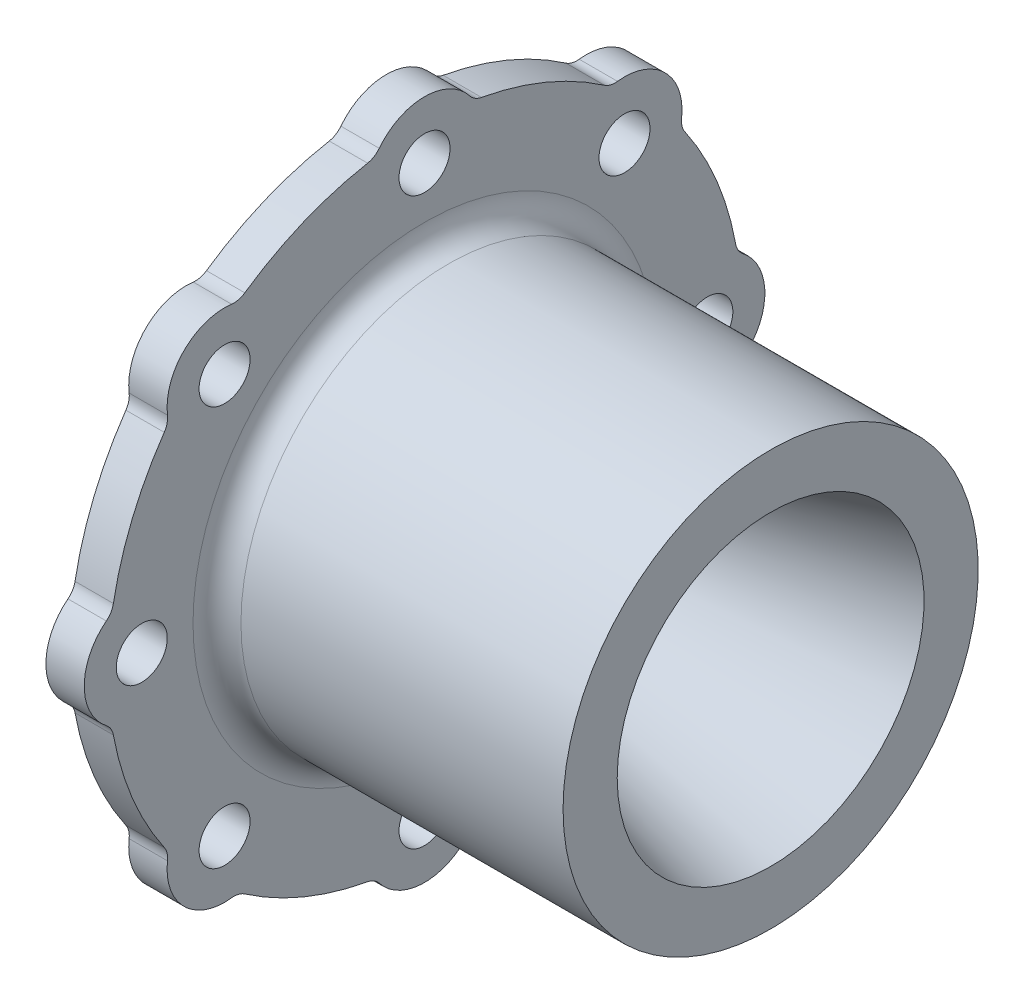
SolidWorks part; units mm, degrees
ref_plane "Front Plane" through (0, 0, 0) normal (0, 0, 1) x (1, 0, 0)
ref_plane "Top Plane" through (0, 0, 0) normal (0, 1, 0) x (1, 0, 0)
ref_plane "Right Plane" through (0, 0, 0) normal (1, 0, 0) x (0, 0, -1)
sketch "Sketch1" plane through (0, 0, 0) normal (0, 0, 1) x (1, 0, 0)
  line L20 (0, 0) -> (32.997, 0) construction
  line L33 (10.9827, 12.3114) -> (21.0157, 12.3114)
  line L34 (10.9827, 12.3114) -> (0, 25.4)
  line L37 (0, 25.4) -> (0, 66.87)
  line L38 (0, 66.87) -> (5.08, 66.87)
  line L39 (5.08, 66.87) -> (5.08, 27.5)
  line L43 (50.9297, 27.5) -> (50.9297, 20.3268)
  line L52 (50.9297, 20.3268) -> (21.0157, 12.3114)
  line L53 (50.9297, 27.5) -> (5.08, 27.5)
  point P1 (2.54, 66.87)
  point P12 (10.9827, 12.3114)
  point P24 (21.0157, 12.3114)
  dimension "D1" = 12.3114
  dimension "D2" = 25.4
  dimension "D5" = 5.08
  dimension "D10" = 15
  dimension "D8" = 20.3268
  dimension "D3" = 27.5
  dimension "D4" = 66.87
  dimension "D6" = 10.033
  dimension "D7" = 50
revolve "Nozzle" add sketch "Sketch1" angle 360 about L20
fillet "Rao outlet radius" radius 4.7029 1 edges at (21.0157, 0, 12.3114)
sketch "Sketch2" plane through (0, 0, 0) normal (-1, 0, 0) x (0, 0, 1)
  point P0 (37.465, 0)
  point P1 (26.4918, -26.4918)
  point P5 (0, -37.465)
  point P6 (-26.4918, -26.4918)
  point P7 (-37.465, 0)
  point P8 (-26.4918, 26.4918)
  point P9 (0, 37.465)
  point P10 (26.4918, 26.4918)
  point P11 (0, 0)
  dimension "D1" = 37.465
hole_wizard "1/4 Clearance Hole1" positions "Sketch2" profile "Sketch3" hole size "1/4" standard "ANSI Inch" end condition through all
sketch "Sketch3" plane through (0, 0, 37.465) normal (0, 1, 0) x (0, 0, 1)
  line L0 (0, 0) -> (0, 50.9297)
  line L1 (0, 50.9297) -> (3.3782, 50.9297)
  line L2 (3.3782, 50.9297) -> (3.3782, 0)
  line L5 (3.3782, 0) -> (0, 0)
  line L11 (0, -6.35) -> (0, 107.95) construction
  dimension "Thru Hole Dia." = 6.7564
  dimension "Thru Hole Depth" = 50.9297
sketch "Sketch5" plane through (0, 0, 0) normal (1, 0, 0) x (0, 0, -1)
  line L0 (0, 0) -> (0, 85.5504) construction
  arc A32 (6.0027, 42.1589) -> (-6.0027, 42.1589) centre (0, 37.465) ccw
  arc A33 (17.8531, 37.9172) -> (7.5462, 41.225) centre (0, 0) ccw
  arc A51 (-7.5462, 41.225) -> (-14.1874, 39.4356) centre (0, 0) ccw
  arc A69 (6.0027, 42.1589) -> (7.5462, 41.225) centre (8.0035, 43.7235) ccw
  arc A70 (-6.0027, 42.1589) -> (-7.5462, 41.225) centre (-8.0035, 43.7235) cw
  arc A72 (34.0554, 25.5663) -> (25.5663, 34.0554) centre (26.4918, 26.4918) ccw
  arc A73 (39.4356, 14.1874) -> (34.4865, 23.8145) centre (0, 0) ccw
  arc A74 (23.8145, 34.4865) -> (17.8531, 37.9172) centre (0, 0) ccw
  arc A75 (34.0554, 25.5663) -> (34.4865, 23.8145) centre (36.5765, 25.2578) ccw
  arc A76 (25.5663, 34.0554) -> (23.8145, 34.4865) centre (25.2578, 36.5765) cw
  arc A77 (42.1589, -6.0027) -> (42.1589, 6.0027) centre (37.465, 0) ccw
  arc A78 (37.9172, -17.8531) -> (41.225, -7.5462) centre (0, 0) ccw
  arc A79 (41.225, 7.5462) -> (39.4356, 14.1874) centre (0, 0) ccw
  arc A80 (42.1589, -6.0027) -> (41.225, -7.5462) centre (43.7235, -8.0035) ccw
  arc A81 (42.1589, 6.0027) -> (41.225, 7.5462) centre (43.7235, 8.0035) cw
  arc A82 (25.5663, -34.0554) -> (34.0554, -25.5663) centre (26.4918, -26.4918) ccw
  arc A83 (14.1874, -39.4356) -> (23.8145, -34.4865) centre (0, 0) ccw
  arc A84 (34.4865, -23.8145) -> (37.9172, -17.8531) centre (0, 0) ccw
  arc A85 (25.5663, -34.0554) -> (23.8145, -34.4865) centre (25.2578, -36.5765) ccw
  arc A86 (34.0554, -25.5663) -> (34.4865, -23.8145) centre (36.5765, -25.2578) cw
  arc A87 (-6.0027, -42.1589) -> (6.0027, -42.1589) centre (0, -37.465) ccw
  arc A88 (-14.2148, -39.4257) -> (-7.5462, -41.225) centre (0, 0) ccw
  arc A89 (7.5462, -41.225) -> (14.1874, -39.4356) centre (0, 0) ccw
  arc A90 (-6.0027, -42.1589) -> (-7.5462, -41.225) centre (-8.0035, -43.7235) ccw
  arc A91 (6.0027, -42.1589) -> (7.5462, -41.225) centre (8.0035, -43.7235) cw
  arc A92 (-34.0554, -25.5663) -> (-25.5663, -34.0554) centre (-26.4918, -26.4918) ccw
  arc A93 (-37.9194, -17.8486) -> (-34.4865, -23.8145) centre (0, 0) ccw
  arc A94 (-23.8145, -34.4865) -> (-14.2148, -39.4257) centre (0, 0) ccw
  arc A95 (-34.0554, -25.5663) -> (-34.4865, -23.8145) centre (-36.5765, -25.2578) ccw
  arc A96 (-25.5663, -34.0554) -> (-23.8145, -34.4865) centre (-25.2578, -36.5765) cw
  arc A97 (-42.1589, 6.0027) -> (-42.1589, -6.0027) centre (-37.465, 0) ccw
  arc A98 (-39.4483, 14.1519) -> (-41.225, 7.5462) centre (0, 0) ccw
  arc A99 (-41.225, -7.5462) -> (-37.9194, -17.8486) centre (0, 0) ccw
  arc A100 (-42.1589, 6.0027) -> (-41.225, 7.5462) centre (-43.7235, 8.0035) ccw
  arc A101 (-42.1589, -6.0027) -> (-41.225, -7.5462) centre (-43.7235, -8.0035) cw
  arc A102 (-25.5663, 34.0554) -> (-34.0554, 25.5663) centre (-26.4918, 26.4918) ccw
  arc A103 (-14.1874, 39.4356) -> (-23.8145, 34.4865) centre (0, 0) ccw
  arc A104 (-34.4865, 23.8145) -> (-39.4483, 14.1519) centre (0, 0) ccw
  arc A105 (-25.5663, 34.0554) -> (-23.8145, 34.4865) centre (-25.2578, 36.5765) ccw
  arc A106 (-34.0554, 25.5663) -> (-34.4865, 23.8145) centre (-36.5765, 25.2578) cw
  point P69 (0, 0)
  point P78 (-6.5261, 41.3988)
  dimension "D3" = 41.91
  dimension "D4" = 2.54
  dimension "D5" = 37.465
  dimension "D6" = 37.465
  dimension "D1" = 8
extrude "Cut-Extrude1" cut sketch "Sketch5" along normal up to surface (5.08 mm away) flip side to cut up to face at (5.08, 0, 40.8432)
fillet "Fillet1" radius 3.175 1 edges at (5.08, 0, 27.5)
fillet "Rao Inlet radius" radius 18.4671 1 edges at (10.9827, 0, 12.3114)
equation "\"radius\"= 1in"
equation "\"Flange\"= 0.55in"
equation "\"Length\"= 2cm"
equation "\"Flange_Thickness\"= 0.2in"
equation "\"offset\"= 0.625cm"
equation "\"D2@Sketch1\"=\"radius\""
equation "\"throat\" = 0.4847in"
equation "\"hole_dia\"= 0.66cm"
equation "\"D1@Sketch1\"=\"throat\""
equation "\"D5@Sketch1\"=\"Flange_Thickness\""
equation "\"Seal_dia\"= 2.5cm"
equation "\"Seal_depth\"= 0.1cm"
equation "\"Seal_width\"= 0.15cm"
equation "\"Nozzle_angle\"= 15"
equation "\"D10@Sketch1\"=\"Nozzle_angle\""
equation "\"nozzle_length\"= 6.34"
equation "\"bolt_head_dia\"=2.3795"
equation "\"bolt_rad\"= \"radius\" + 0.5 * \"Flange\" + 0.2in"
equation "\"scallop_inner_dia\"= 3.3in"
equation "\"exit_rad\"= 1.693cm"
equation "\"D8@Sketch1\"=\"throat\"*(2.726)^0.5"
equation "\"outside_dia\"= 2.75cm"
equation "\"D3@Sketch1\"=\"outside_dia\""
equation "\"D4@Sketch1\"=\"outside_dia\"+\"Flange\"+\"Buffer\""
equation "\"Scallop_OD\"= 0.6in"
equation "\"D3\"= \"Scallop_OD\" / 2"
equation "\"D4\"= \"scallop_inner_dia\" / 2"
equation "\"D2@Sketch5\"=\"Scallop_OD\"/2"
equation "\"D3@Sketch5\"=\"scallop_inner_dia\"/2"
equation "\"D6@Sketch5\"=\"bolt_rad\""
equation "\"D1@Sketch2\"=\"bolt_rad\""
equation "\"Buffer\"= 1in"
equation "\"D1@Rao Inlet radius\"=3*\"throat\""
equation "\"D1@Rao outlet radius\"= 0.382 * \"throat\""
equation "\"D1@Rao Inlet radius\"=1.5*\"throat\""
